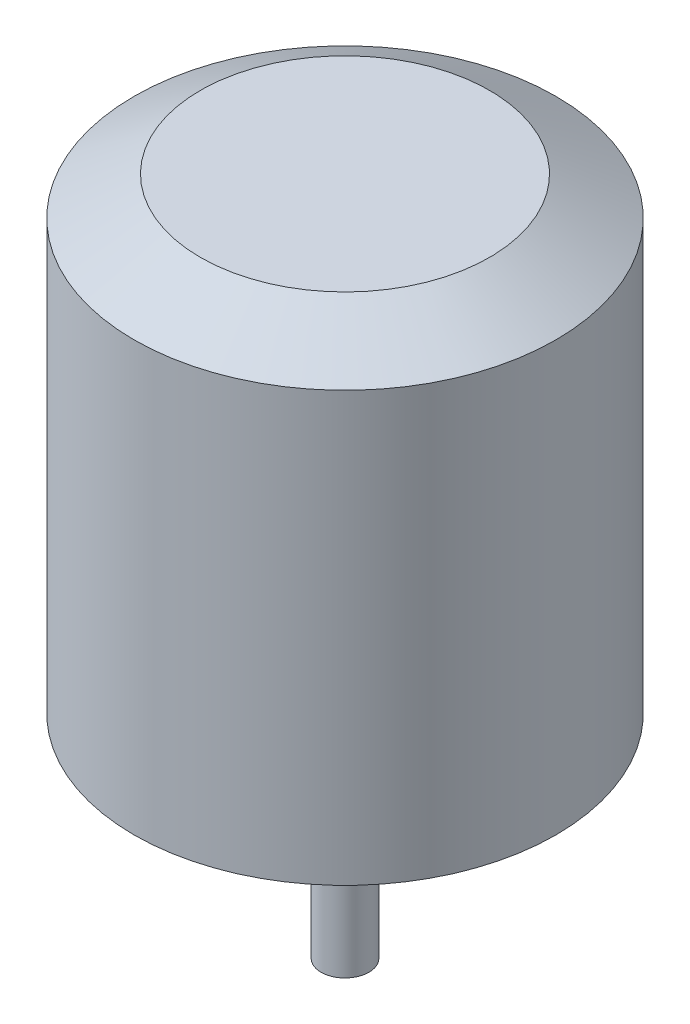
SolidWorks part; units mm, degrees
ref_plane "Front Plane" through (0, 0, 0) normal (0, 0, 1) x (1, 0, 0)
ref_plane "Top Plane" through (0, 0, 0) normal (0, 1, 0) x (1, 0, 0)
ref_plane "Right Plane" through (0, 0, 0) normal (1, 0, 0) x (0, 0, -1)
other "Bounding Box"
ref_plane "Default Plane" through (-8.9266, -12.7485, 0) normal (-0.1736, 0.9848, 0) x (0.9848, 0.1736, 0)
sketch "Sketch1" plane through (0, 0, 0) normal (0, 1, 0) x (1, 0, 0)
  circle A0 centre (0, 0) radius 14
  dimension "D1" = 28
extrude "Boss-Extrude1" add sketch "Sketch1" along normal mid plane 31
chamfer "Chamfer1" distance 2.54 angle 60 1 edges at (0, 15.5, 14) first distance on face at (0, 15.5, 14)
sketch "Sketch2" plane through (0, -15.5, 0) normal (0, -1, 0) x (1, 0, 0)
  circle A0 centre (0, 0) radius 1.5875
  dimension "D1" = 3.175
extrude "Boss-Extrude2" add sketch "Sketch2" along normal offset from surface (14.1 mm away) 45.1 up to face at (0, 15.5, 9.6006)
